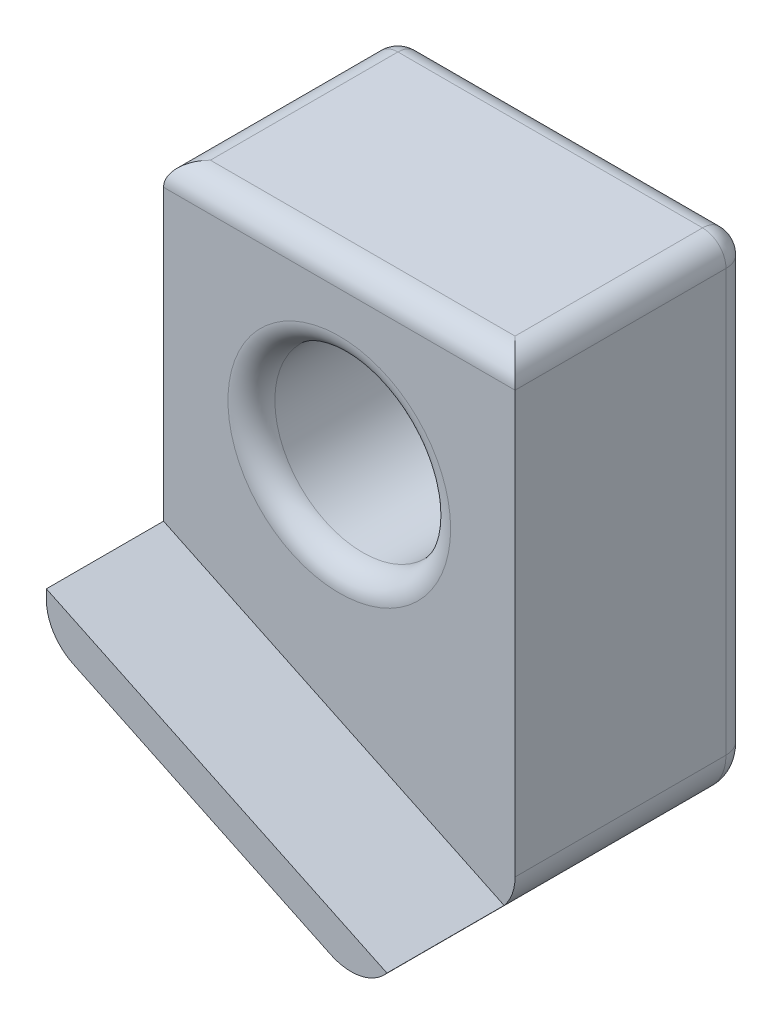
SolidWorks part; units mm, degrees
ref_plane "Front Plane" through (0, 0, 0) normal (0, 0, 1) x (1, 0, 0)
ref_plane "Top Plane" through (0, 0, 0) normal (0, 1, 0) x (1, 0, 0)
ref_plane "Right Plane" through (0, 0, 0) normal (1, 0, 0) x (0, 0, -1)
sketch "Sketch1" plane through (0, 0, 0) normal (0, 0, 1) x (1, 0, 0)
  line L0 (-7.5, 0) -> (-7.5, 7.5)
  line L1 (2.0352, 3.525) -> (-2.0352, 3.525) construction
  line L2 (-2.0352, 3.525) -> (-4.0703, 0) construction
  line L3 (-4.0703, 0) -> (-2.0352, -3.525) construction
  line L4 (-2.0352, -3.525) -> (2.0352, -3.525) construction
  line L5 (2.0352, -3.525) -> (4.0703, 0) construction
  line L6 (4.0703, 0) -> (2.0352, 3.525) construction
  line L7 (-7.5, 7.5) -> (7.5, 7.5)
  line L8 (7.5, 7.5) -> (7.5, 0)
  circle A0 centre (0, 0) radius 3.525 construction
  circle A1 centre (0, 0) radius 3.75
  arc A2 (-7.5, 0) -> (7.5, 0) centre (0, 0) ccw
  dimension "D2" = 7.5
  dimension "D3" = 7.5
  dimension "D1" = 7.05
  dimension "D4" = 15
extrude "Boss-Extrude1" add sketch "Sketch1" along normal blind 10
sketch "Sketch2" plane through (0, 0, 0) normal (0, 0, -1) x (-1, 0, 0)
  line L0 (-7.5, 0) -> (-7.5, -14.6587)
  line L1 (-7.5, -14.6587) -> (7.5, -7.5014)
  line L2 (7.5, -7.5014) -> (7.5, 0)
  line L3 (7.5, 7.5) -> (7.5, 0) construction
  line L4 (-7.5, 0) -> (-7.5, 7.5) construction
  line L5 (-126.518, -69.2329) -> (43.6074, 11.9435) construction
  arc A0 (7.5, 0) -> (-7.5, 0) centre (0, 0) cw
  dimension "D1" = 2
extrude "Boss-Extrude2" add sketch "Sketch2" against normal through all
sketch "Sketch3" plane through (0, 0, 10) normal (0, 0, 1) x (1, 0, 0)
  line L0 (-7.5, -5.2854) -> (7.5, -12.4427) construction
  line L1 (126.518, -69.2329) -> (-43.6074, 11.9435) construction
  line L2 (-7.5, 7.5) -> (-7.5, -7.5014) construction
  line L3 (7.5, -14.6587) -> (7.5, 7.5) construction
  line L4 (7.5, -12.9967) -> (7.5, -14.6587)
  line L5 (7.5, -14.6587) -> (-7.5, -7.5014)
  line L6 (-7.5, -7.5014) -> (-7.5, -5.8394)
  line L7 (-7.5, -5.8394) -> (7.5, -12.9967)
  dimension "D1" = 0.5
extrude "Boss-Extrude3" add sketch "Sketch3" along normal blind 5
fillet "Fillet1" radius 2 2 edges at (-7.5, -7.5014, 7.5) (7.5, -14.6587, 7.5)
fillet "Fillet2" radius 1 10 edges at (3.75, 0, 10) (7.5, -1.9942, 0) (6.5671, -13.1799, 0) (-7.5, 0.6302, 0) (-7.1915, -7.3068, 0) (0, 7.5, 10) (0, 7.5, 0) (-0.8613, -10.6691, 0) (-7.5, 7.5, 5) (7.5, 7.5, 5)
